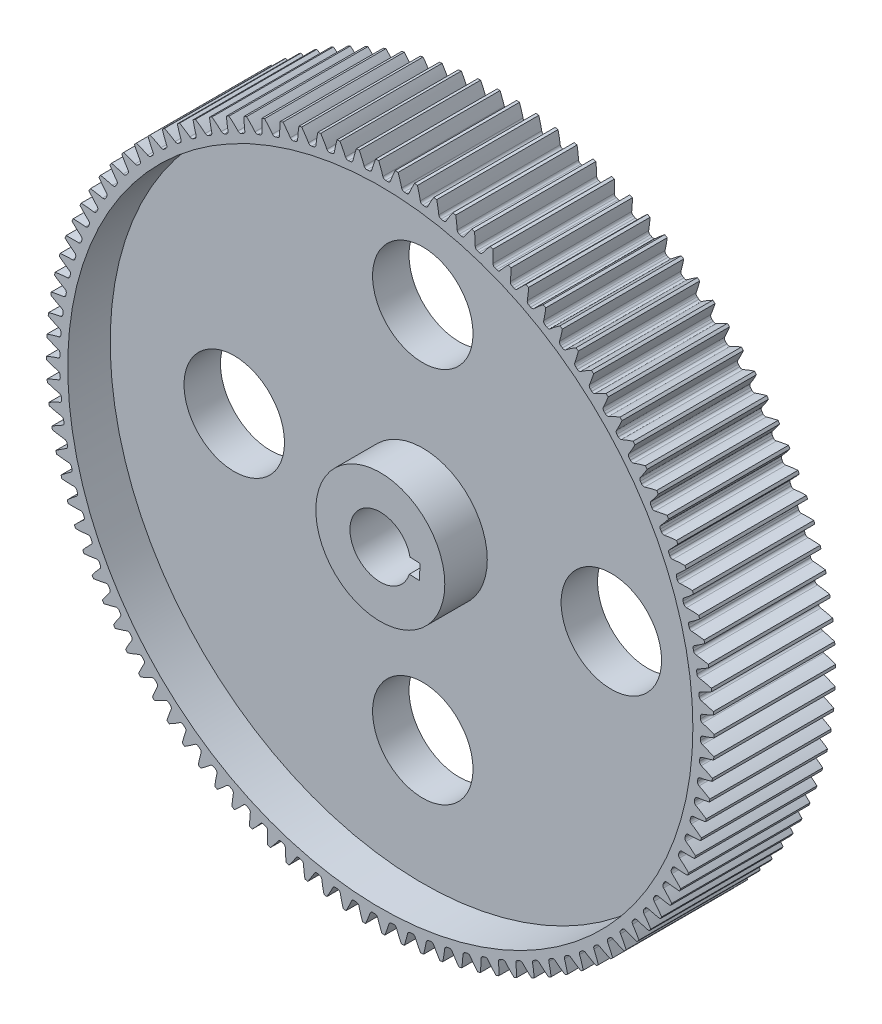
SolidWorks part; units mm, degrees
material "AISI 1045 Steel, cold drawn"
ref_plane "Front" through (0, 0, 0) normal (0, 0, 1) x (1, 0, 0)
ref_plane "Top" through (0, 0, 0) normal (0, 1, 0) x (1, 0, 0)
ref_plane "Right" through (0, 0, 0) normal (1, 0, 0) x (0, 0, -1)
sketch "Sketch3" plane through (0, 0, 0) normal (0, 0, 1) x (1, 0, 0)
  circle A0 centre (0, 0) radius 110
  dimension "od" = 220
extrude "gearBody" add sketch "Sketch3" along normal blind 40
sketch "Sketch2" plane through (0, 0, 0) normal (0, 0, 1) x (1, 0, 0)
  line L0 (0, 0) -> (93.7616, 38.8373) construction
  line L1 (127.4135, -20.4616) -> (0, 0) construction
  line L2 (0, 0) -> (36.3143, 0) construction
  line L3 (107.9997, -0.2438) -> (107.9247, -4.033) construction
  line L5 (107.9622, -2.1384) -> (0, 0) construction
  line L7 (0, 0) -> (101.4868, 0) construction
  arc A0 (101.4664, -2.0368) -> (101.4674, -1.9826) centre (0, 0) ccw construction
  arc A1 (109.9987, 0.5436) -> (109.8909, -4.8988) centre (0, 0) ccw construction
  arc A2 (107.9997, -0.2438) -> (107.9247, -4.033) centre (0, 0) ccw construction
  arc A3 (105.521, -2.4383) -> (105.5348, -1.742) centre (0, 0) ccw
  arc A4 (127.4135, -20.4616) -> (106.1493, -3.3522) centre (92.1502, -42.5196) ccw
  arc A5 (127.4135, -20.4616) -> (128.1238, 15.4003) centre (0, 0) ccw
  arc A6 (128.1238, 15.4003) -> (106.1987, -0.8536) centre (93.7616, 38.8373) cw
  arc A7 (105.5348, -1.742) -> (106.1987, -0.8536) centre (106.482, -1.7576) cw
  arc A8 (106.1493, -3.3522) -> (105.521, -2.4383) centre (106.4681, -2.4602) cw
  point P6 (128.1238, 15.4003)
  point P22 (127.4135, -20.4616)
  dimension "baseDia" = 202.9736
  dimension "od" = 220
  dimension "pd" = 216
  dimension "rd" = 211.0984
  dimension "rFillet" = 0.9473
  dimension "pointX" = 128.1238
  dimension "pointY" = 15.4003
  dimension "CTT" = 3.7892
  dimension "flankCenterAngle" = 22.5
extrude "toothCut" cut sketch "Sketch2" along normal through all
pattern_circular "CirPattern1" count 108 over 360 about axis through (0, 0, 40) along (0, 0, -1) of "toothCut"
ref_axis "toothSpace" through (0, 0, 0) along (0.9998, -0.0198, 0)
ref_axis "Axis2" through (109.8685, -5.3761, 0) along (-0.9988, 0.0489, 0)
sketch "hub1Dia" plane through (0, 0, 0) normal (0, 0, -1) x (-1, 0, 0)
  circle A0 centre (0, 0) radius 0.5
  dimension "hub1Dia" = 1
sketch "hub2Dia" plane through (0, 0, 40) normal (0, 0, 1) x (1, 0, 0)
  circle A0 centre (0, 0) radius 0.5
  dimension "hub2dia" = 1
sketch "boreDia" plane through (0, 0, 0) normal (0, 0, 1) x (1, 0, 0)
  circle A0 centre (0, 0) radius 10
  dimension "boreDia" = 20
extrude "bore" cut sketch "boreDia" against normal mid plane 25400
sketch "kwy1sketch" plane through (0, 0, 0) normal (0, 0, 1) x (1, 0, 0)
  line L0 (-5.3237, 0.2605) -> (0, 0) construction
  line L1 (13.1066, 1.8617) -> (12.8623, -3.1324)
  line L2 (12.8623, -3.1324) -> (6.6198, -2.8269)
  line L3 (13.1066, 1.8617) -> (6.8641, 2.1671)
  line L4 (6.6198, -2.8269) -> (0, 0)
  line L5 (0, 0) -> (6.8641, 2.1671)
  line L6 (0, 0) -> (105.5285, -2.0901) construction
  line L7 (12.9845, -0.6354) -> (0, 0) construction
  arc A7 (105.521, -2.4383) -> (105.5348, -1.742) centre (0, 0) ccw construction
  point P9 (12.9845, -0.6354)
  point P13 (-0.8881, 0.0435)
  dimension "kwy1width" = 5
  dimension "kwy1depth" = 13
  dimension "kwy1angle" = 1.667
  dimension "kwy1Depth2" = 6.25
extrude "kwy1" cut sketch "kwy1sketch" against normal mid plane 12700
sketch "kwy2sketch" plane through (0, 0, 0) normal (0, 0, 1) x (1, 0, 0)
  line L0 (105.5285, -2.0901) -> (0, 0) construction
  line L1 (0, 0) -> (-2.7287, -2.4741) construction
  line L2 (7.9514, 10.5842) -> (11.3099, 6.8801)
  line L3 (11.3099, 6.8801) -> (6.6798, 2.6819)
  line L4 (7.9514, 10.5842) -> (3.3213, 6.386)
  line L5 (6.6798, 2.6819) -> (0, 0)
  line L6 (0, 0) -> (3.3213, 6.386)
  arc A2 (105.521, -2.4383) -> (105.5348, -1.742) centre (0, 0) ccw construction
  point P10 (9.6307, 8.7321)
  dimension "kwy2angle" = 43.333
  dimension "kwy2Width" = 5
  dimension "kwy2depth" = 13
  dimension "kwy2Depth2" = 6.25
sketch "kwy3sketch" plane through (0, 0, 0) normal (0, 0, 1) x (1, 0, 0)
  line L0 (105.5285, -2.0901) -> (0, 0) construction
  line L1 (0, 0) -> (-0.1302, -2.6615) construction
  line L2 (-1.8617, 13.1066) -> (3.1324, 12.8623)
  line L3 (3.1324, 12.8623) -> (2.8269, 6.6198)
  line L4 (-1.8617, 13.1066) -> (-2.1671, 6.8641)
  line L5 (2.8269, 6.6198) -> (0, 0)
  line L6 (-2.1671, 6.8641) -> (0, 0)
  point P10 (0.6354, 12.9845)
  dimension "kwy3angle" = 88.333
  dimension "kwy3depth" = 13
  dimension "kwy3width" = 5
  dimension "kwy3Depth2" = 6.25
sketch "kwy4sketch" plane through (0, 0, 0) normal (0, 0, 1) x (1, 0, 0)
  line L0 (105.5285, -2.0901) -> (0, 0) construction
  line L1 (0, 0) -> (1.3995, -1.5435) construction
  line L2 (-6.8801, 11.3099) -> (-10.5842, 7.9514)
  line L3 (-10.5842, 7.9514) -> (-6.386, 3.3213)
  line L4 (-6.386, 3.3213) -> (0, 0)
  line L5 (-2.6819, 6.6798) -> (0, 0)
  line L6 (-6.8801, 11.3099) -> (-2.6819, 6.6798)
  point P15 (-8.7321, 9.6307)
  dimension "kwy4angle" = 133.333
  dimension "kwy4depth" = 13
  dimension "kwy4width" = 5
  dimension "kwy4Depth2" = 6.25
sketch "kwy5sketch" plane through (0, 0, 0) normal (0, 0, 1) x (1, 0, 0)
  line L0 (105.5285, -2.0901) -> (0, 0) construction
  line L1 (0, 0) -> (1.7873, -0.0875) construction
  line L2 (-12.8623, 3.1324) -> (-13.1066, -1.8617)
  line L3 (-13.1066, -1.8617) -> (-6.8641, -2.1671)
  line L4 (-12.8623, 3.1324) -> (-6.6198, 2.8269)
  line L5 (-6.8641, -2.1671) -> (0, 0)
  line L6 (-6.6198, 2.8269) -> (0, 0)
  point P10 (-12.9845, 0.6354)
  dimension "kwy5width" = 5
  dimension "kwy5depth" = 13
  dimension "kwy5angle" = 178.333
  dimension "kwy5Depth2" = 6.25
sketch "kwy6sketch" plane through (0, 0, 0) normal (0, 0, 1) x (1, 0, 0)
  line L0 (105.5285, -2.0901) -> (0, 0) construction
  line L1 (0, 0) -> (1.3246, 1.201) construction
  line L2 (-11.3099, -6.8801) -> (-7.9514, -10.5842)
  line L3 (-7.9514, -10.5842) -> (-3.3213, -6.386)
  line L4 (-11.3099, -6.8801) -> (-6.6798, -2.6819)
  line L5 (-3.3213, -6.386) -> (0, 0)
  line L6 (-6.6798, -2.6819) -> (0, 0)
  point P10 (-9.6307, -8.7321)
  dimension "kwy6angle" = 223.333
  dimension "kwy6width" = 5
  dimension "kwy6depth" = 13
  dimension "kwy6Depth2" = 6.25
sketch "kwy7sketch" plane through (0, 0, 0) normal (0, 0, 1) x (1, 0, 0)
  line L0 (105.5285, -2.0901) -> (0, 0) construction
  line L1 (0, 0) -> (0.0979, 2.0007) construction
  line L2 (-3.1324, -12.8623) -> (1.8617, -13.1066)
  line L3 (-3.1324, -12.8623) -> (-2.8269, -6.6198)
  line L4 (1.8617, -13.1066) -> (2.1671, -6.8641)
  line L5 (-2.8269, -6.6198) -> (0, 0)
  line L6 (2.1671, -6.8641) -> (0, 0)
  point P10 (-0.6354, -12.9845)
  dimension "kwy7angle" = 88.333
  dimension "kwy7width" = 5
  dimension "kwy7depth" = 13
  dimension "kwy7angle1" = 268.333
  dimension "kwy7Depth2" = 6.25
sketch "kwy8sketch" plane through (0, 0, 0) normal (0, 0, 1) x (1, 0, 0)
  line L0 (105.5285, -2.0901) -> (0, 0) construction
  line L1 (0, 0) -> (-1.1954, 1.3184) construction
  line L2 (6.8801, -11.3099) -> (10.5842, -7.9514)
  line L3 (10.5842, -7.9514) -> (6.386, -3.3213)
  line L4 (6.8801, -11.3099) -> (2.6819, -6.6798)
  line L5 (6.386, -3.3213) -> (0, 0)
  line L6 (2.6819, -6.6798) -> (0, 0)
  point P10 (8.7321, -9.6307)
  dimension "kwy8angle" = 313.333
  dimension "kwy8width" = 5
  dimension "kwy8depth" = 13
  dimension "kwy8Depth2" = 6.25
sketch "centerLine" plane through (0, 0, 0) normal (0, 1, 0) x (1, 0, 0)
  line L0 (0, 36.4807) -> (0, -59.6309) construction
ref_plane "CB1plane" through (0, 0, 0) normal (0, 0, -1) x (-1, 0, 0)
sketch "CB1diameter" plane through (0, 0, 0) normal (0, 0, -1) x (-1, 0, 0)
  circle A0 centre (0, 0) radius 0.5
  dimension "CB1diameter" = 1
ref_plane "CB2plane" through (0, 0, 40) normal (0, 0, 1) x (1, 0, 0)
sketch "CB2diameter" plane through (0, 0, 40) normal (0, 0, 1) x (1, 0, 0)
  circle A0 centre (0, 0) radius 0.5
  dimension "CB2diameter" = 1
ref_axis "Axis1" through (0, 0, 50) along (0, 0, -1)
sketch3d "3DSketch1" plane through (0, 0, 0) normal (0, 0, 1) x (1, 0, 0)
sketch "Sketch4" plane through (0, 0, 0) normal (0, 0, -1) x (-1, 0, 0)
  circle A0 centre (0, 0) radius 21.25
  circle A1 centre (0, 0) radius 103
  dimension "D1" = 42.5
  dimension "D2" = 206
extrude "Cut-Extrude1" cut sketch "Sketch4" against normal blind 14
sketch "Sketch5" plane through (0, 0, 40) normal (0, 0, 1) x (1, 0, 0)
  circle A0 centre (0, 0) radius 21.25
  circle A1 centre (0, 0) radius 103
  dimension "D1" = 206
  dimension "D2" = 42.5
extrude "Cut-Extrude2" cut sketch "Sketch5" against normal blind 14
sketch "Sketch6" plane through (0, 0, 26) normal (0, 0, 1) x (1, 0, 0)
  circle A0 centre (0, -62.125) radius 16.55
  circle A1 centre (62.125, 0) radius 16.55
  circle A2 centre (0, 62.125) radius 16.55
  circle A3 centre (-62.125, 0) radius 16.55
  dimension "D1" = 33.1
  dimension "D2" = 33.1
  dimension "D3" = 33.1
  dimension "D4" = 33.1
  dimension "D5" = 124.25
  dimension "D6" = 124.25
  dimension "D7" = 62.125
  dimension "D8" = 62.125
extrude "Cut-Extrude3" cut sketch "Sketch6" against normal blind 14
